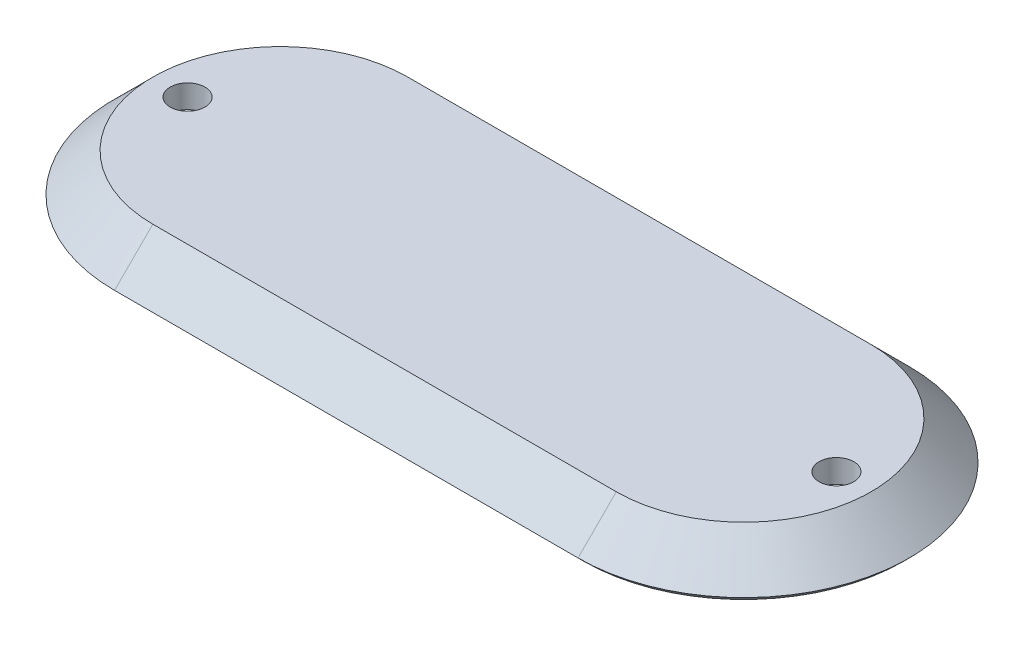
SolidWorks part; units mm, degrees
ref_plane "Plan de face" through (0, 0, 0) normal (0, 0, 1) x (1, 0, 0)
ref_plane "Plan de dessus" through (0, 0, 0) normal (0, 1, 0) x (1, 0, 0)
ref_plane "Plan de droite" through (0, 0, 0) normal (1, 0, 0) x (0, 0, -1)
sketch "Esquisse1" plane through (0, 0, 0) normal (0, 1, 0) x (1, 0, 0)
  line L0 (-20, 0) -> (20, 0) construction
  line L1 (-20, 14.8) -> (20, 14.8)
  line L2 (-20, -14.8) -> (20, -14.8)
  arc A0 (-20, 14.8) -> (-20, -14.8) centre (-20, 0) ccw
  arc A1 (20, -14.8) -> (20, 14.8) centre (20, 0) ccw
  point P3 (0, 0)
  dimension "D1" = 14.8
  dimension "D2" = 40
extrude "Boss.-Extru.1" add sketch "Esquisse1" along normal blind 3.8 draft 45
shell "Coque2" thickness 2 removed face at (0, 0, 0)
chamfer "Chanfrein1" distance 1 angle 45 4 edges at (-34.8, 0, 0) (0, 0, 14.8) (0, 0, -14.8) (34.8, 0, 0) first distance on face at (0, 0, 0)
sketch "Esquisse2" plane through (0, 3.8, 0) normal (0, 1, 0) x (1, 0, 0)
  line L0 (0, 11) -> (0, -11) construction
  line L1 (20, 11) -> (-20, 11) construction
  line L2 (-20, -11) -> (20, -11) construction
  circle A0 centre (-28, 0) radius 1.5
  circle A1 centre (28, 0) radius 1.5
  point P2 (0, 0)
  dimension "D1" = 3
  dimension "D2" = 8
extrude "Enlèv. mat.-Extru.1" cut sketch "Esquisse2" against normal up to next
